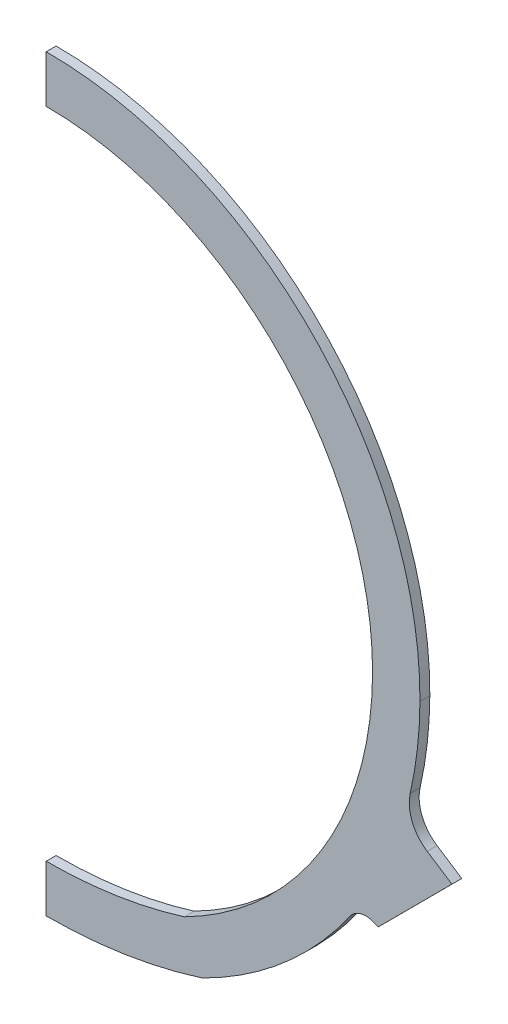
SolidWorks part; units mm, degrees
material "Balsa"
ref_plane "Front Plane" through (0, 0, 0) normal (0, 0, 1) x (1, 0, 0)
ref_plane "Top Plane" through (0, 0, 0) normal (0, 1, 0) x (1, 0, 0)
ref_plane "Right Plane" through (0, 0, 0) normal (1, 0, 0) x (0, 0, -1)
sketch "Sketch2" plane through (0, 0, 0) normal (0, 0, 1) x (1, 0, 0)
  line L0 (0, 0) -> (0.688, 245.4392) construction
  line L1 (-0.1309, -46.7153) -> (-0.2841, -101.3462) construction
  line L2 (0.0534, 19.05) -> (-169.3081, 19.05) construction
  line L3 (-72.7218, -93.726) -> (74.7111, -93.726) construction
  arc A1 (-120.0989, 19.05) -> (120.2036, 18.3433) centre (0.0534, 19.05) cw
  arc A2 (-120.0989, 19.05) -> (-50.0584, -93.726) centre (5.7147, 19.05) ccw
  arc A3 (-50.0584, -93.726) -> (50.1388, -93.726) centre (0.0402, 63.5) ccw
  arc A4 (120.2036, 18.3433) -> (50.1388, -93.726) centre (-5.6406, 19.0835) cw
  arc A5 (-104.8589, 19.05) -> (104.9639, 18.4329) centre (0.0534, 19.05) cw
  arc A6 (104.9639, 18.4329) -> (44.4049, -79.5534) centre (-5.6406, 19.0835) cw
  arc A7 (-44.324, -79.5535) -> (44.4049, -79.5534) centre (0.0402, 63.5) ccw
  arc A8 (-104.8589, 19.05) -> (-44.324, -79.5535) centre (5.7147, 19.05) ccw
  spline S0 degree 3 poles (-7457.5243, 7873.9786) (-1520.6447, 792.6716) (-232.684, -284.717) (69.4764, -82.4823) (75.8596, -77.7331) (81.7614, -72.3621) (85.2966, -68.8071) (85.996, -68.0862) (87.3792, -66.6243) (88.0639, -65.8824) (90.0847, -63.6371) (91.3894, -62.1126) (95.1787, -57.4581) (97.5389, -54.2471) (101.9343, -47.6137) (103.9694, -44.1914) (106.7765, -38.8981) (107.6712, -37.107) (109.3772, -33.4707) (110.1904, -31.6207) (112.481, -26.0415) (113.8153, -22.2742) (116.1105, -14.6467) (117.0712, -10.7866) (118.62, -2.9737) (119.208, 0.9791) (119.8028, 6.9796) (119.953, 8.9949) (120.1541, 13.0067) (120.2055, 15.0081) (120.2151, 20.9991) (119.8425, 28.9519) (118.7088, 36.835) (117.5685, 42.7208) (117.1399, 44.6783) (116.1841, 48.5842) (115.6559, 50.5346) (113.94, 56.3082) (112.6165, 60.0751) (109.6192, 67.4485) (107.9453, 71.055) (104.2453, 78.1066) (102.2192, 81.5518) (99.4588, 85.754) (98.8945, 86.5903) (97.7468, 88.2466) (97.1639, 89.0659) (95.3883, 91.4977) (94.1686, 93.0841) (90.4034, 97.7402) (87.752, 100.7072) (82.1689, 106.369) (79.2371, 109.0639) (74.6247, 112.8977) (73.0514, 114.1408) (70.6363, 115.9521) (69.821, 116.5478) (68.1799, 117.7153) (67.3537, 118.2875) (63.1947, 121.0918) (59.7778, 123.1535) (52.769, 126.9212) (49.1769, 128.6272) (41.816, 131.6806) (38.0473, 133.028) (33.2217, 134.4796) (32.2518, 134.758) (30.3116, 135.2882) (29.34, 135.5404) (26.4206, 136.2591) (24.4685, 136.6873) (18.5945, 137.8219) (14.6552, 138.3782) (6.7301, 139.0933) (2.7444, 139.252) (-2.2675, 139.1959) (-3.2714, 139.172) (-5.2821, 139.0983) (-6.2905, 139.0484) (-9.3072, 138.8606) (-11.3068, 138.6846) (-17.272, 138.0072) (-25.1357, 136.7069) (-32.823, 134.6274) (-38.5216, 132.7724) (-40.41, 132.1048) (-44.1641, 130.6694) (-46.0326, 129.9002) (-538.3584, -87.5727) (554.8292, -3549.2971) (3251.8348, -10297.372) knots -2.787439 -2.787439 -2.787439 -2.787439 0.03125 0.03125 0.0625 0.09375 0.09375 0.101563 0.101563 0.109375 0.109375 0.125 0.125 0.15625 0.15625 0.1875 0.1875 0.203125 0.203125 0.21875 0.21875 0.25 0.25 0.28125 0.28125 0.3125 0.3125 0.328125 0.328125 0.34375 0.34375 0.375 0.40625 0.40625 0.421875 0.421875 0.4375 0.4375 0.46875 0.46875 0.5 0.5 0.53125 0.53125 0.539063 0.539063 0.546875 0.546875 0.5625 0.5625 0.59375 0.59375 0.625 0.625 0.640625 0.640625 0.648438 0.648438 0.65625 0.65625 0.6875 0.6875 0.71875 0.71875 0.75 0.75 0.757813 0.757813 0.765625 0.765625 0.78125 0.78125 0.8125 0.8125 0.84375 0.84375 0.851563 0.851563 0.859375 0.859375 0.875 0.875 0.90625 0.9375 0.9375 0.953125 0.953125 0.96875 0.96875 5.126469 5.126469 5.126469 5.126469 only from (55.8537, -90.8749) to (-58.6671, 123.6507)
  spline S1 degree 3 poles (55.8537, -90.8749) (59.4151, -88.9779) (62.8499, -86.9173) (69.4764, -82.4823) (75.8596, -77.7331) (81.7614, -72.3621) (85.2966, -68.8071) (85.996, -68.0862) (87.3792, -66.6243) (88.0639, -65.8824) (90.0847, -63.6371) (91.3894, -62.1126) (95.1787, -57.4581) (97.5389, -54.2471) (101.9343, -47.6137) (103.9694, -44.1914) (106.7765, -38.8981) (107.6712, -37.107) (109.3772, -33.4707) (110.1904, -31.6207) (112.481, -26.0415) (113.8153, -22.2742) (116.1105, -14.6467) (117.0712, -10.7866) (118.62, -2.9737) (119.208, 0.9791) (119.8028, 6.9796) (119.953, 8.9949) (120.1541, 13.0067) (120.2055, 15.0081) (120.2151, 20.9991) (119.8425, 28.9519) (118.7088, 36.835) (117.5685, 42.7208) (117.1399, 44.6783) (116.1841, 48.5842) (115.6559, 50.5346) (113.94, 56.3082) (112.6165, 60.0751) (109.6192, 67.4485) (107.9453, 71.055) (104.2453, 78.1066) (102.2192, 81.5518) (99.4588, 85.754) (98.8945, 86.5903) (97.7468, 88.2466) (97.1639, 89.0659) (95.3883, 91.4977) (94.1686, 93.0841) (90.4034, 97.7402) (87.752, 100.7072) (82.1689, 106.369) (79.2371, 109.0639) (74.6247, 112.8977) (73.0514, 114.1408) (70.6363, 115.9521) (69.821, 116.5478) (68.1799, 117.7153) (67.3537, 118.2875) (63.1947, 121.0918) (59.7778, 123.1535) (52.769, 126.9212) (49.1769, 128.6272) (41.816, 131.6806) (38.0473, 133.028) (33.2217, 134.4796) (32.2518, 134.758) (30.3116, 135.2882) (29.34, 135.5404) (26.4206, 136.2591) (24.4685, 136.6873) (18.5945, 137.8219) (14.6552, 138.3782) (6.7301, 139.0933) (2.7444, 139.252) (-2.2675, 139.1959) (-3.2714, 139.172) (-5.2821, 139.0983) (-6.2905, 139.0484) (-9.3072, 138.8606) (-11.3068, 138.6846) (-17.272, 138.0072) (-25.1357, 136.7069) (-32.823, 134.6274) (-38.5216, 132.7724) (-40.41, 132.1048) (-44.1641, 130.6694) (-46.0326, 129.9002) (-51.5624, 127.4576) (-55.1595, 125.6458) (-58.6671, 123.6507) knots 0 0 0 0 0.03125 0.03125 0.0625 0.09375 0.09375 0.101563 0.101563 0.109375 0.109375 0.125 0.125 0.15625 0.15625 0.1875 0.1875 0.203125 0.203125 0.21875 0.21875 0.25 0.25 0.28125 0.28125 0.3125 0.3125 0.328125 0.328125 0.34375 0.34375 0.375 0.40625 0.40625 0.421875 0.421875 0.4375 0.4375 0.46875 0.46875 0.5 0.5 0.53125 0.53125 0.539063 0.539063 0.546875 0.546875 0.5625 0.5625 0.59375 0.59375 0.625 0.625 0.640625 0.640625 0.648438 0.648438 0.65625 0.65625 0.6875 0.6875 0.71875 0.71875 0.75 0.75 0.757813 0.757813 0.765625 0.765625 0.78125 0.78125 0.8125 0.8125 0.84375 0.84375 0.851563 0.851563 0.859375 0.859375 0.875 0.875 0.90625 0.9375 0.9375 0.953125 0.953125 0.96875 0.96875 1 1 1 1 construction
  spline S2 degree 3 poles (7698.4035, -7600.8615) (1611.4613, -764.0515) (222.821, 341.9355) (-76.9523, 111.0297) (-81.0984, 107.3558) (-85.9766, 102.3921) (-86.9369, 101.3807) (-88.8267, 99.3202) (-89.7577, 98.2691) (-92.4915, 95.0728) (-94.2304, 92.8907) (-99.2026, 86.1952) (-102.1931, 81.5333) (-106.1993, 74.2476) (-107.4545, 71.77) (-109.2154, 67.9791) (-109.782, 66.7031) (-110.874, 64.1258) (-111.4002, 62.8224) (-113.9097, 56.2871) (-115.5417, 50.9767) (-118.0823, 40.1978) (-118.9908, 34.7292) (-119.6657, 27.7928) (-119.7775, 26.4005) (-119.9543, 23.6055) (-120.0192, 22.2016) (-120.1418, 18.0057) (-120.1286, 15.2199) (-119.8102, 6.8959) (-119.2278, 1.3912) (-117.8014, -6.7994) (-117.2335, -9.5184) (-116.2404, -13.58) (-115.8858, -14.9311) (-115.1288, -17.6274) (-114.7258, -18.9739) (-112.6063, -25.6411) (-108.5276, -35.9696) (-103.1136, -45.6397) (-99.3011, -51.4722) (-98.5171, -52.628) (-96.9053, -54.9182) (-96.0765, -56.0537) (-93.5433, -59.4015) (-91.7865, -61.5635) (-86.3167, -67.8444) (-82.4051, -71.759) (-76.1398, -77.2217) (-73.9848, -78.9742) (-70.6503, -81.498) (-69.5218, -82.3217) (-67.2303, -83.9337) (-66.0665, -84.7222) (591.775, -513.8293) (4465.0583, 6093.4616) (-858.1872, -7414.6277) knots -4.145324 -4.145324 -4.145324 -4.145324 0.0625 0.0625 0.125 0.125 0.140625 0.140625 0.15625 0.15625 0.1875 0.1875 0.25 0.25 0.28125 0.28125 0.296875 0.296875 0.3125 0.3125 0.375 0.375 0.4375 0.4375 0.453125 0.453125 0.46875 0.46875 0.5 0.5 0.5625 0.5625 0.59375 0.59375 0.609375 0.609375 0.625 0.625 0.6875 0.75 0.75 0.765625 0.765625 0.78125 0.78125 0.8125 0.8125 0.875 0.875 0.90625 0.90625 0.921875 0.921875 0.9375 0.9375 9.693438 9.693438 9.693438 9.693438 only from (-58.6671, 123.6507) to (-50.3455, -93.5936)
  spline S3 degree 3 poles (-6093.8521, 8949.2565) (1657.017, -4470.2733) (1699.3783, -2108.1952) (-3189.6914, 10349.9889) knots -230.213154 -230.213154 -230.213154 -230.213154 248.242551 248.242551 248.242551 248.242551 only from (49.819, -93.8744) to (55.8537, -90.8749)
  spline S4 degree 3 poles (49.819, -93.8744) (51.8584, -92.9316) (53.87, -91.9317) (55.8537, -90.8749) knots 0 0 0 0 1 1 1 1 construction
  spline S5 degree 3 poles (-58.6671, 123.6507) (-63.5487, 120.874) (-68.1774, 117.7887) (-76.9523, 111.0297) (-81.0984, 107.3558) (-85.9766, 102.3921) (-86.9369, 101.3807) (-88.8267, 99.3202) (-89.7577, 98.2691) (-92.4915, 95.0728) (-94.2304, 92.8907) (-99.2026, 86.1952) (-102.1931, 81.5333) (-106.1993, 74.2476) (-107.4545, 71.77) (-109.2154, 67.9791) (-109.782, 66.7031) (-110.874, 64.1258) (-111.4002, 62.8224) (-113.9097, 56.2871) (-115.5417, 50.9767) (-118.0823, 40.1978) (-118.9908, 34.7292) (-119.6657, 27.7928) (-119.7775, 26.4005) (-119.9543, 23.6055) (-120.0192, 22.2016) (-120.1418, 18.0057) (-120.1286, 15.2199) (-119.8102, 6.8959) (-119.2278, 1.3912) (-117.8014, -6.7994) (-117.2335, -9.5184) (-116.2404, -13.58) (-115.8858, -14.9311) (-115.1288, -17.6274) (-114.7258, -18.9739) (-112.6063, -25.6411) (-108.5276, -35.9696) (-103.1136, -45.6397) (-99.3011, -51.4722) (-98.5171, -52.628) (-96.9053, -54.9182) (-96.0765, -56.0537) (-93.5433, -59.4015) (-91.7865, -61.5635) (-86.3167, -67.8444) (-82.4051, -71.759) (-76.1398, -77.2217) (-73.9848, -78.9742) (-70.6503, -81.498) (-69.5218, -82.3217) (-67.2303, -83.9337) (-66.0665, -84.7222) (-60.2073, -88.5441) (-55.3561, -91.2432) (-50.3455, -93.5936) knots 0 0 0 0 0.0625 0.0625 0.125 0.125 0.140625 0.140625 0.15625 0.15625 0.1875 0.1875 0.25 0.25 0.28125 0.28125 0.296875 0.296875 0.3125 0.3125 0.375 0.375 0.4375 0.4375 0.453125 0.453125 0.46875 0.46875 0.5 0.5 0.5625 0.5625 0.59375 0.59375 0.609375 0.609375 0.625 0.625 0.6875 0.75 0.75 0.765625 0.765625 0.78125 0.78125 0.8125 0.8125 0.875 0.875 0.90625 0.90625 0.921875 0.921875 0.9375 0.9375 1 1 1 1 construction
  spline S6 degree 3 poles (-2482.9215, 10606.6105) (134.4304, 111.18) (111.5262, -73.4925) (45.8458, -95.3665) (44.8322, -95.6594) (41.7708, -96.4587) (39.7032, -96.8873) (35.5384, -97.6293) (33.4392, -97.9405) (29.2422, -98.4783) (27.1412, -98.7049) (20.8322, -99.2882) (16.6185, -99.55) (8.1799, -99.8877) (3.9548, -99.9623) (-4.5058, -99.9387) (-8.734, -99.8405) (-17.1695, -99.4557) (-21.3793, -99.1705) (-27.6778, -98.553) (-29.7745, -98.3152) (-33.9608, -97.7556) (-36.0504, -97.4344) (-39.177, -96.8603) (-40.2191, -96.653) (-42.292, -96.1992) (-43.3225, -95.953) (-45.3676, -95.407) (-46.3821, -95.1076) (-112.5445, -72.6554) (-128.1138, 114.0017) (2927.5642, 10491.2531) knots -1.983598 -1.983598 -1.983598 -1.983598 0.03125 0.03125 0.0625 0.0625 0.125 0.125 0.1875 0.1875 0.25 0.25 0.375 0.375 0.5 0.5 0.625 0.625 0.75 0.75 0.8125 0.8125 0.875 0.875 0.90625 0.90625 0.9375 0.9375 0.96875 0.96875 3.000363 3.000363 3.000363 3.000363 only from (49.8185, -93.8746) to (-50.3451, -93.5938)
  spline S7 degree 3 poles (49.8185, -93.8746) (48.8452, -94.325) (47.8521, -94.6984) (45.8458, -95.3665) (44.8322, -95.6594) (41.7708, -96.4587) (39.7032, -96.8873) (35.5384, -97.6293) (33.4392, -97.9405) (29.2422, -98.4783) (27.1412, -98.7049) (20.8322, -99.2882) (16.6185, -99.55) (8.1799, -99.8877) (3.9548, -99.9623) (-4.5058, -99.9387) (-8.734, -99.8405) (-17.1695, -99.4557) (-21.3793, -99.1705) (-27.6778, -98.553) (-29.7745, -98.3152) (-33.9608, -97.7556) (-36.0504, -97.4344) (-39.177, -96.8603) (-40.2191, -96.653) (-42.292, -96.1992) (-43.3225, -95.953) (-45.3676, -95.407) (-46.3821, -95.1076) (-48.3867, -94.4274) (-49.3773, -94.0483) (-50.3451, -93.5938) knots 0 0 0 0 0.03125 0.03125 0.0625 0.0625 0.125 0.125 0.1875 0.1875 0.25 0.25 0.375 0.375 0.5 0.5 0.625 0.625 0.75 0.75 0.8125 0.8125 0.875 0.875 0.90625 0.90625 0.9375 0.9375 0.96875 0.96875 1 1 1 1 construction
  spline S8 degree 1 poles (44.4895, -82.3468) (49.8828, -79.6661) knots 0 0 1 1 construction
  spline S9 degree 1 poles (49.8828, -79.6661) (-52.388, 112.6115) knots 0 0 1 1 construction
  spline S10 degree 1 poles (-52.388, 112.6115) (-44.952, -82.0958) knots 0 0 1 1 construction
  spline S11 degree 3 poles (44.4895, -82.3468) (44.9451, -82.1361) (45.8533, -81.7084) (47.2062, -81.0479) (48.5497, -80.3682) (49.4396, -79.9022) (49.8828, -79.6661) knots 0 0 0 0 0.250007 0.500014 0.750021 1.000028 1.000028 1.000028 1.000028 construction
  spline S12 degree 3 poles (49.8828, -79.6661) (51.4682, -78.8216) (54.6039, -77.0481) (60.6329, -73.2256) (67.7713, -67.9145) (75.6946, -60.7068) (85.376, -49.946) (92.2499, -39.5527) (97.0635, -29.9209) (99.9774, -23.2906) (102.9687, -14.8438) (105.5551, -4.452) (106.8747, 4.4138) (107.4138, 11.642) (107.598, 18.8242) (107.1791, 27.7507) (105.6575, 38.3493) (103.0737, 48.9109) (99.5091, 59.0529) (95.0071, 68.7524) (90.4672, 76.4728) (86.3465, 82.4205) (79.7918, 90.9419) (71.0678, 99.805) (59.5047, 108.4813) (50.3361, 114.0108) (40.7123, 118.5824) (32.2831, 121.5955) (25.3334, 123.4944) (18.366, 125.0225) (9.571, 126.2643) (-1.0997, 126.6912) (-11.9104, 126.0185) (-22.4327, 124.2743) (-36.1547, 120.5693) (-46.1487, 116.1604) (-52.388, 112.6115) knots 0 0 0 0 0.015625 0.03125 0.0625 0.09375 0.125 0.1875 0.203125 0.21875 0.25 0.28125 0.3125 0.328125 0.34375 0.375 0.40625 0.4375 0.46875 0.5 0.53125 0.546875 0.5625 0.625 0.65625 0.6875 0.71875 0.75 0.765625 0.78125 0.8125 0.84375 0.875 0.90625 0.9375 1 1 1 1 construction
  spline S13 degree 3 poles (-52.388, 112.6115) (-54.5585, 111.3769) (-58.8261, 108.7475) (-66.8816, 102.9693) (-76.1597, 94.757) (-85.9932, 83.258) (-92.681, 72.8203) (-97.1816, 63.9424) (-101.112, 54.6656) (-104.776, 42.7383) (-106.8137, 30.488) (-107.4512, 20.4245) (-107.4028, 10.4189) (-106.3564, 0.5368) (-104.3212, -9.2152) (-101.5955, -18.9231) (-97.0158, -30.5128) (-90.9605, -41.334) (-85.1677, -49.567) (-78.8706, -57.3154) (-71.8665, -64.3232) (-64.1621, -70.5906) (-57.9948, -74.9291) (-51.5954, -78.7902) (-47.193, -81.0446) (-44.952, -82.0958) knots 0 0 0 0 0.03125 0.0625 0.125 0.1875 0.25 0.28125 0.3125 0.375 0.4375 0.46875 0.5 0.5625 0.59375 0.625 0.6875 0.75 0.78125 0.8125 0.875 0.90625 0.9375 0.96875 1 1 1 1 construction
  spline S14 degree 1 poles (44.4849, -82.3489) (-44.9469, -82.0982) knots 0 0 1 1 construction
  spline S15 degree 3 poles (44.4849, -82.3489) (44.3746, -82.3999) (44.1627, -82.4934) (43.6492, -82.7012) (42.8561, -82.9839) (41.7841, -83.3184) (40.2245, -83.7477) (38.1103, -84.2445) (35.4106, -84.7656) (32.6063, -85.224) (28.7759, -85.7537) (23.885, -86.2821) (17.9201, -86.7432) (11.8971, -87.0512) (5.8396, -87.2261) (-2.2666, -87.2864) (-10.3738, -87.0974) (-18.3985, -86.6419) (-24.3556, -86.1481) (-29.2377, -85.5934) (-33.056, -85.0443) (-35.8555, -84.5718) (-38.5671, -84.0318) (-40.6899, -83.5223) (-42.2517, -83.0828) (-43.3238, -82.7417) (-44.1147, -82.4546) (-44.6269, -82.2439) (-44.8373, -82.1497) (-44.9469, -82.0982) knots 0 0 0 0 0.007812 0.015625 0.03125 0.046875 0.0625 0.09375 0.125 0.15625 0.1875 0.25 0.3125 0.375 0.4375 0.5 0.625 0.6875 0.75 0.8125 0.84375 0.875 0.90625 0.9375 0.953125 0.96875 0.984375 0.992188 1 1 1 1 construction
  point P12 (-0.2802, -99.9505)
  dimension "D3" = 19.05
  dimension "D4" = 93.726
  dimension "D5" = 63.5
  dimension "D6" = 15.24
  dimension "D1" = 12.7
  dimension "D2" = 12.7
extrude "Boss-Extrude1" add sketch "Sketch2" along normal mid plane 3.175
sketch "Sketch3" plane through (0, 0, 0) normal (1, 0, 0) x (0, 0, -1)
  line L1 (-100.0568, 212.3798) -> (108.5889, 212.3798)
  line L2 (-100.0568, 212.3798) -> (-100.0568, -170.6472)
  line L3 (-100.0568, -170.6472) -> (108.5889, -170.6472)
  line L4 (108.5889, 212.3798) -> (108.5889, -170.6472)
extrude "Cut-Extrude1" cut sketch "Sketch3" against normal through all
sketch "Sketch5" plane through (0, 0, 0) normal (0, 0, 1) x (1, 0, 0)
  line L1 (106.7372, -51.2419) -> (130.4908, -27.4216)
  line L2 (130.4908, -27.4216) -> (114.8436, -17.2602)
  line L3 (106.7372, -51.2419) -> (100.526, -48.4884)
  line L4 (100.526, -48.4884) -> (114.8436, -17.2602)
  line L5 (0, 1.0565) -> (259.101, 1.0565) construction
  arc A0 (50.1388, -93.726) -> (120.2036, 18.3433) centre (-5.6406, 19.0835) ccw construction
  ellipse E1 centre (0, 100.0263) end of major axis (100.6018, 100.0263) minor radius 98.9698 (0, 1.0565) -> (0, 198.9961) ccw construction
  dimension "D1" = 33
  dimension "D2" = 23.908
  dimension "D3" = 45.08
  dimension "D4" = 112.5089
  dimension "D5" = 28.4781
  dimension "D6" = 33.6398
  dimension "D7" = 6.7941
extrude "Boss-Extrude2" add sketch "Sketch5" along normal mid plane 3.175
fillet "Fillet1" radius 6.35 1 edges at (100.526, -48.4884, 0)
fillet "Fillet2" radius 12.7 1 edges at (114.8436, -17.2602, 0)
